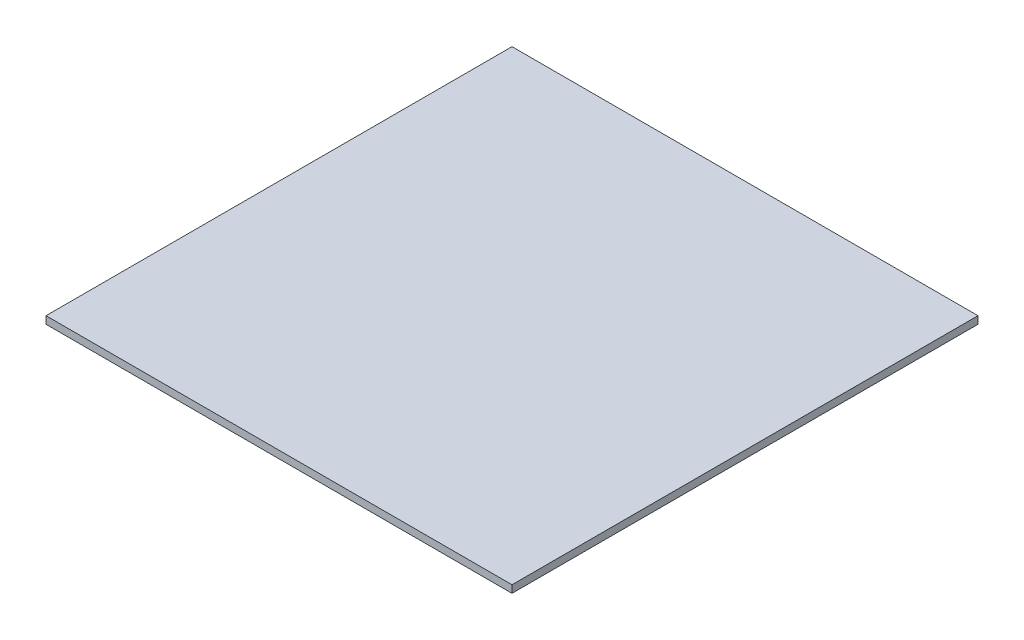
SolidWorks part; units mm, degrees
ref_plane "Front Plane" through (0, 0, 0) normal (0, 0, 1) x (1, 0, 0)
ref_plane "Top Plane" through (0, 0, 0) normal (0, 1, 0) x (1, 0, 0)
ref_plane "Right Plane" through (0, 0, 0) normal (1, 0, 0) x (0, 0, -1)
sketch "Sketch1" plane through (0, 0, 0) normal (0, 1, 0) x (1, 0, 0)
  line L1 (0, 0) -> (250, 0)
  line L2 (0, 0) -> (0, 250)
  line L3 (0, 250) -> (250, 250)
  line L4 (250, 0) -> (250, 250)
  dimension "D1" = 250
  dimension "D2" = 250
extrude "Boss-Extrude1" add sketch "Sketch1" along normal blind 4
equation "\"cf_tube_outer_diameter\" = 25mm"
equation "\"cf_tube_inner_diameter\" = 21mm"
equation "\"mid_plate_mid_to_top\" = 100mm"
equation "\"mid_plate_mid_to_bottom\" = 30mm"
equation "\"mid_plate_horizontal_spacing\" = 250mm"
equation "\"cf_plate_thickness\" = 4mm"
equation "\"mid_tube_length\" = 500mm"
equation "\"mid_plate_bottom_width\"= 150mm"
equation "\"D1@Sketch1\"=\"mid_plate_horizontal_spacing\""
equation "\"mid_support_plate_distance\" = 250mm"
equation "\"D2@Sketch1\"=\"mid_support_plate_distance\""
equation "\"D1@Boss-Extrude1\"=\"cf_plate_thickness\""
